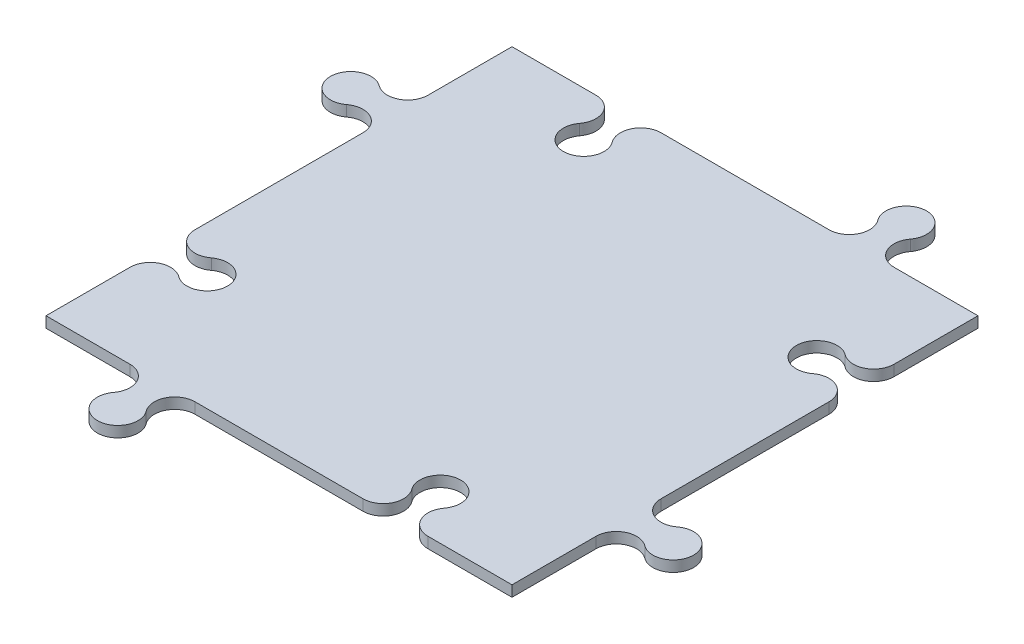
SolidWorks part; units mm, degrees
note: The reader was unsure of these and kept them because the rebuilt part matched: shared geometry of "Sketch2<3>".
ref_plane "Front Plane" through (0, 0, 0) normal (0, 0, 1) x (1, 0, 0)
ref_plane "Top Plane" through (0, 0, 0) normal (0, 1, 0) x (1, 0, 0)
ref_plane "Right Plane" through (0, 0, 0) normal (1, 0, 0) x (0, 0, -1)
sketch "Sketch1" plane through (0, 0, 0) normal (0, 1, 0) x (1, 0, 0)
  line L1 (68.2, -68.2) -> (-68.2, -68.2)
  line L2 (68.2, -68.2) -> (68.2, 68.2)
  line L3 (68.2, 68.2) -> (-68.2, 68.2)
  line L4 (-68.2, -68.2) -> (-68.2, 68.2)
  line L5 (68.2, -68.2) -> (-68.2, 68.2) construction
  line L6 (68.2, 68.2) -> (-68.2, -68.2) construction
  circle A0 centre (0, 0) radius 55.5 construction
  circle A1 centre (0, 0) radius 68.2 construction
  dimension "D1" = 111
  dimension "D2" = 12.7
extrude "Boss-Extrude1" add sketch "Sketch1" along normal blind 3.175 contours L4 L3 L2 L1
sketch "Sketch2" plane through (0, 0, 0) normal (0, 1, 0) x (1, 0, 0)
  line L0 (-68.2, 34.1) -> (-113.1129, 34.1) construction
  line L1 (-68.2, 43.625) -> (-68.2, 24.575)
  line L2 (-68.2, -68.2) -> (-68.2, 68.2) construction
  line L3 (0, 0) -> (-68.2, 0) construction
  line L4 (68.2, 68.2) -> (-68.2, -68.2) construction
  line L5 (-68.2, -43.625) -> (-68.2, -24.575)
  arc A0 (-77.725, 29.3375) -> (-87.25, 34.1) centre (-81.2969, 34.1) cw
  arc A1 (-77.725, 29.3375) -> (-68.2, 24.575) centre (-74.1531, 24.575) cw
  arc A2 (-77.725, 38.8625) -> (-68.2, 43.625) centre (-74.1531, 43.625) ccw
  arc A3 (-77.725, -29.3375) -> (-68.2, -24.575) centre (-74.1531, -24.575) ccw construction
  arc A4 (-77.725, 38.8625) -> (-87.25, 34.1) centre (-81.2969, 34.1) ccw
  arc A5 (-77.725, -29.3375) -> (-87.25, -34.1) centre (-81.2969, -34.1) ccw construction
  arc A6 (-77.725, -38.8625) -> (-87.25, -34.1) centre (-81.2969, -34.1) cw construction
  arc A7 (-77.725, -38.8625) -> (-68.2, -43.625) centre (-74.1531, -43.625) cw construction
  arc A8 (-58.675, -38.8625) -> (-68.2, -43.625) centre (-62.2469, -43.625) ccw
  arc A9 (-58.675, -38.8625) -> (-49.15, -34.1) centre (-55.1031, -34.1) ccw
  arc A10 (-58.675, -29.3375) -> (-49.15, -34.1) centre (-55.1031, -34.1) cw
  arc A11 (-58.675, -29.3375) -> (-68.2, -24.575) centre (-62.2469, -24.575) cw
  point P19 (-77.9803, 24.575)
  point P22 (-77.9803, 43.625)
  dimension "D1" = 19.05
  dimension "D2" = 19.05
extrude "Boss-Extrude2" add sketch "Sketch2" along normal up to surface (3.175 mm away) contours A0 A4 A2 L1 A1 up to face at (0, 3.175, 0)
extrude "Cut-Extrude2" cut sketch "Sketch2<3>" along normal through all contours L5 A11 A10 A9 A8
sketch "Sketch2<3>" plane through (0, 0, 0) normal (0, 1, 0) x (1, 0, 0) same geometry as "Sketch2"
sketch "Sketch3" plane through (0, 0, 0) normal (0, 0, 1) x (1, 0, 0)
  line L0 (0, 0) -> (0, 29.4045) construction
  line L1 (68.2, 0) -> (-68.2, 0) construction
pattern_circular "CirPattern1" count 4 over 360 about axis through (0, 0, 0) along (0, 1, 0) of "Boss-Extrude2", "Cut-Extrude2"
